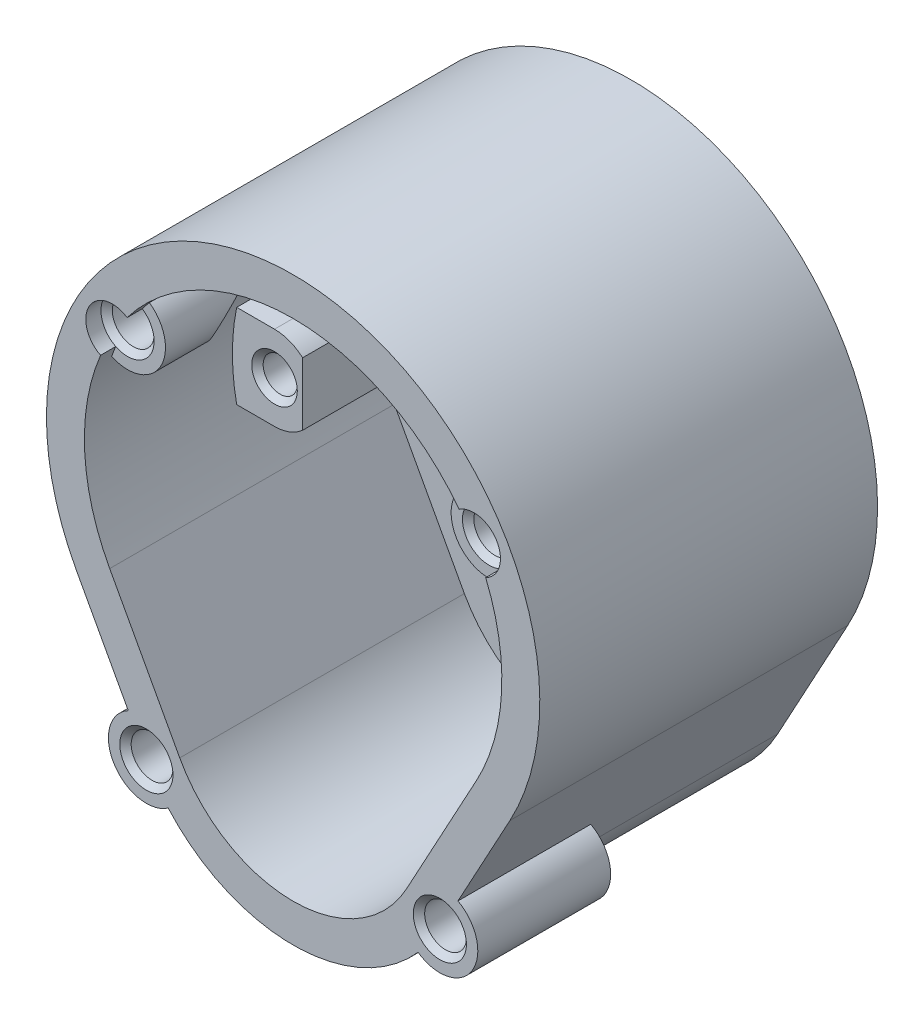
SolidWorks part; units mm, degrees
material "PET"
ref_plane "Front Plane" through (0, 0, 0) normal (0, 0, 1) x (1, 0, 0)
ref_plane "Top Plane" through (0, 0, 0) normal (0, 1, 0) x (1, 0, 0)
ref_plane "Right Plane" through (0, 0, 0) normal (1, 0, 0) x (0, 0, -1)
sketch "Sketch1" plane through (0, 0, 0) normal (0, 0, 1) x (1, 0, 0)
  line L0 (-28.5595, -15.5114) -> (-19.3326, -32.5)
  line L1 (28.5595, -15.5114) -> (19.3326, -32.5)
  line L2 (0, 0) -> (0, -22) construction
  arc A0 (28.5595, -15.5114) -> (-28.5595, -15.5114) centre (0, 0) ccw
  arc A1 (-19.3326, -32.5) -> (19.3326, -32.5) centre (0, -22) ccw
  dimension "D1" = 65
  dimension "D2" = 22
  dimension "D3" = 44
extrude "Boss-Extrude1" add sketch "Sketch1" along normal blind 7
sketch "Sketch2" plane through (0, 0, 7) normal (0, 0, 1) x (1, 0, 0)
  line L0 (0, 0) -> (0, -22) construction
  circle A0 centre (0, -22) radius 2.75
  dimension "D1" = 22
  dimension "D2" = 5.5
extrude "Cut-Extrude1" cut sketch "Sketch2" against normal through all
sketch "Sketch3" plane through (0, 0, 7) normal (0, 0, 1) x (1, 0, 0)
  circle A0 centre (0, -22) radius 7.1
  dimension "D1" = 14.2
extrude "Cut-Extrude2" cut sketch "Sketch3" against normal blind 5
sketch "Sketch4" plane through (0, 0, 7) normal (0, 0, 1) x (1, 0, 0)
  line L0 (-28.5595, -15.5114) -> (-19.3326, -32.5)
  line L1 (28.5595, -15.5114) -> (19.3326, -32.5)
  line L2 (-24.1658, -13.125) -> (-14.9388, -30.1136)
  line L3 (24.1658, -13.125) -> (14.9388, -30.1136)
  arc A0 (28.5595, -15.5114) -> (-28.5595, -15.5114) centre (0, 0) ccw
  arc A1 (-19.3326, -32.5) -> (19.3326, -32.5) centre (0, -22) ccw
  arc A2 (28.5595, -15.5114) -> (-28.5595, -15.5114) centre (0, 0) ccw construction
  arc A3 (-19.3326, -32.5) -> (19.3326, -32.5) centre (0, -22) ccw construction
  arc A4 (24.1658, -13.125) -> (-24.1658, -13.125) centre (0, 0) ccw
  arc A5 (-14.9388, -30.1136) -> (14.9388, -30.1136) centre (0, -22) ccw
  dimension "D1" = 5
extrude "Boss-Extrude2" add sketch "Sketch4" along normal blind 37.5
sketch "Sketch5" plane through (0, 0, 7) normal (0, 0, 1) x (1, 0, 0)
  line L0 (-21.95, 0) -> (21.95, 0) construction
  line L1 (-21.95, 5.55) -> (-26.9341, 5.55)
  line L2 (-21.95, -5.55) -> (-26.9341, -5.55)
  line L3 (21.95, 5.55) -> (26.9341, 5.55)
  line L4 (21.95, -5.55) -> (26.9341, -5.55)
  circle A0 centre (-21.95, 0) radius 2.25
  circle A1 centre (21.95, 0) radius 2.25
  arc A2 (-21.95, -5.55) -> (-21.95, 5.55) centre (-21.95, 0) ccw
  arc A3 (21.95, 5.55) -> (21.95, -5.55) centre (21.95, 0) ccw
  arc A4 (-26.9341, 5.55) -> (-26.9341, -5.55) centre (0, 0) ccw
  arc A5 (24.1658, -13.125) -> (-24.1658, -13.125) centre (0, 0) ccw construction
  arc A6 (26.9341, -5.55) -> (26.9341, 5.55) centre (0, 0) ccw
  dimension "D1" = 4.5
  dimension "D2" = 4.5
  dimension "D3" = 43.9
extrude "Boss-Extrude3" add sketch "Sketch5" along normal blind 18
sketch "Sketch6" plane through (0, 0, 7) normal (0, 0, 1) x (1, 0, 0)
  line L0 (-12, 15.95) -> (-12, -1.05) construction
  line L1 (-12, -1.05) -> (12, -1.05) construction
  line L2 (-12, 15.95) -> (12, 15.95) construction
  circle A0 centre (-12, 15.95) radius 1.6
  circle A1 centre (12, 15.95) radius 1.6
  circle A2 centre (-12, -1.05) radius 1.6
  circle A3 centre (12, -1.05) radius 1.6
  dimension "D1" = 3.2
  dimension "D2" = 3.2
  dimension "D3" = 3.2
  dimension "D4" = 3.2
  dimension "D6" = 15.95
  dimension "D5" = 12
  dimension "D7" = 24
  dimension "D8" = 24
  dimension "D9" = 17
extrude "Cut-Extrude3" cut sketch "Sketch6" against normal up to next
sketch "Sketch7" plane through (0, 0, 44.5) normal (0, 0, 1) x (1, 0, 0)
  line L1 (0, 0) -> (0, -44) construction
  line L2 (0, 0) -> (23.8157, 13.75) construction
  line L3 (0, 0) -> (-23.8157, 13.75) construction
  line L5 (0, 0) -> (-19.3326, -32.5) construction
  line L6 (0, 0) -> (19.3326, -32.5) construction
  circle A1 centre (-23.8157, 13.75) radius 5
  arc A2 (26.9341, 5.55) -> (-26.9341, 5.55) centre (0, 0) ccw construction
  circle A3 centre (23.8157, 13.75) radius 5
  arc A4 (24.1658, -13.125) -> (-24.1658, -13.125) centre (0, 0) ccw construction
  arc A6 (-19.3326, -32.5) -> (19.3326, -32.5) centre (0, -22) ccw construction
  arc A7 (28.5595, -15.5114) -> (-28.5595, -15.5114) centre (0, 0) ccw construction
  circle A10 centre (-19.3326, -32.5) radius 5
  circle A11 centre (19.3326, -32.5) radius 5
  dimension "D3" = 10
  dimension "D4" = 10
  dimension "D1" = 120
  dimension "D2" = 120
extrude "Boss-Extrude4" add sketch "Sketch7" against normal blind 17.5
sketch "Sketch9" plane through (0, 0, 0) normal (1, 0, 0) x (0, 0, -1)
  line L0 (-27, 27.5) -> (-35.6603, 22.5)
  line L1 (-35.6603, 22.5) -> (-27, 22.5)
  line L2 (-27, 22.5) -> (-27, 27.5)
  line L3 (0, 32.5) -> (-44.5, 32.5) construction
  line L4 (-44.5, 32.5) -> (-44.5, -15.5114) construction
  line L5 (0, 0) -> (-44.5, 0) construction
  dimension "D1" = 5
  dimension "D2" = 5
  dimension "D3" = 30
  dimension "D4" = 17.5
revolve "Cut-Revolve2" cut sketch "Sketch9" angle 145 mid plane about L5
sketch "Sketch10" plane through (0, 0, 44.5) normal (0, 0, 1) x (1, 0, 0)
  line L0 (-24.1658, -13.125) -> (-14.9388, -30.1136)
  line L1 (24.1658, -13.125) -> (14.9388, -30.1136)
  arc A0 (24.1658, -13.125) -> (-24.1658, -13.125) centre (0, 0) ccw
  arc A1 (-14.9388, -30.1136) -> (14.9388, -30.1136) centre (0, -22) ccw
extrude "Cut-Extrude4" cut sketch "Sketch10" against normal blind 2
sketch "Sketch11" plane through (0, 0, 44.5) normal (0, 0, 1) x (1, 0, 0)
  circle A0 centre (-23.8157, 13.75) radius 2.75
  arc A1 (-20.9324, 17.8349) -> (-25.9117, 9.2105) centre (0, 0) ccw construction
  circle A2 centre (23.8157, 13.75) radius 2.75
  arc A3 (25.9117, 9.2105) -> (20.9324, 17.8349) centre (0, 0) ccw construction
  circle A5 centre (-19.3326, -32.5) radius 2.75
  circle A6 centre (19.3326, -32.5) radius 2.75
  dimension "D1" = 5.5
  dimension "D2" = 5.5
  dimension "D3" = 5.5
  dimension "D4" = 5.5
extrude "Cut-Extrude6" cut sketch "Sketch11" against normal blind 12
sketch "Sketch12" plane through (0, 0, 0) normal (0, 0, -1) x (-1, 0, 0)
  line L0 (4.2, -33.55) -> (-5.3, -33.55) construction
  circle A0 centre (4.2, -33.55) radius 1.5
  circle A1 centre (0, -22) radius 2.75 construction
  circle A2 centre (-5.3, -33.55) radius 1.5
  dimension "D2" = 11.55
  dimension "D3" = 3
  dimension "D5" = 3
  dimension "D1" = 4.2
  dimension "D4" = 9.5
extrude "Cut-Extrude7" cut sketch "Sketch12" against normal up to next
chamfer "Chamfer1" distance 2 angle 45 4 edges at (13.6, 15.95, 7) (13.6, -1.05, 7) (-10.4, -1.05, 7) (-10.4, 15.95, 7)
sketch "Sketch13" plane through (0, 0, 25) normal (0, 0, 1) x (1, 0, 0)
  line L1 (18.25, -4.1367) -> (-18.25, -4.1367)
  line L2 (18.25, -4.1367) -> (18.25, 4.1367)
  line L3 (18.25, 4.1367) -> (-18.25, 4.1367)
  line L4 (-18.25, -4.1367) -> (-18.25, 4.1367)
  line L5 (18.25, -4.1367) -> (-18.25, 4.1367) construction
  line L6 (18.25, 4.1367) -> (-18.25, -4.1367) construction
  arc A1 (-21.95, -5.55) -> (-21.95, 5.55) centre (-21.95, 0) ccw construction
  point P0 (0, 0)
  dimension "D1" = 36.5
extrude "Cut-Extrude9" cut sketch "Sketch13" against normal up to surface (18 mm away) up to face at (15.6, 15.95, 7)
chamfer "Chamfer2" distance 0.75 angle 45 6 edges at (-5.7, -33.55, 0) (3.8, -33.55, 0) (24.2, 0, 25) (-19.7, 0, 25) (22.0826, -32.5, 44.5) (-16.5826, -32.5, 44.5)
sketch "Sketch14" plane through (0, 0, 44.5) normal (0, 0, 1) x (1, 0, 0)
  circle A0 centre (-23.8157, 13.75) radius 3.5
  circle A1 centre (23.8157, 13.75) radius 3.5
  dimension "D1" = 7
  dimension "D2" = 7
extrude "Cut-Extrude10" cut sketch "Sketch14" against normal up to surface (2 mm away) up to face at (-22.0195, 12.713, 42.5)
chamfer "Chamfer3" distance 0.75 angle 45 2 edges at (26.5657, 13.75, 42.5) (-21.0657, 13.75, 42.5)
